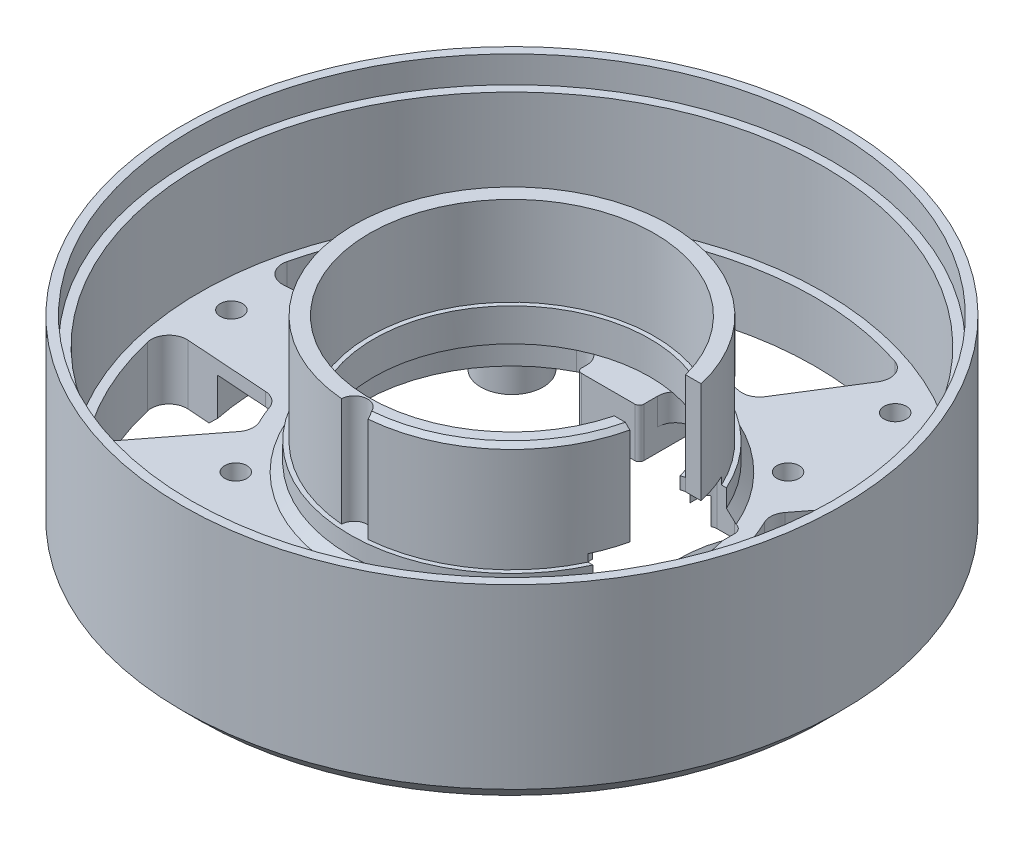
SolidWorks part; units mm, degrees
ref_plane "Front Plane" through (0, 0, 0) normal (0, 0, 1) x (1, 0, 0)
ref_plane "Top Plane" through (0, 0, 0) normal (0, 1, 0) x (1, 0, 0)
ref_plane "Right Plane" through (0, 0, 0) normal (1, 0, 0) x (0, 0, -1)
ref_axis "Axis1" through (0, 0, 0) along (0, 1, 0)
sketch "Sketch1" plane through (0, 0, 0) normal (0, 0, 1) x (1, 0, 0)
  line L0 (0, 0) -> (0, -50277.2651) construction
  line L1 (-17.7, 6) -> (-17.7, -6.2)
  line L2 (-17.7, -6.2) -> (-18.2, -6.2)
  line L3 (-18.2, -6.2) -> (-18.2, -8.2)
  line L4 (-19.2, -9.2) -> (-35, -9.2)
  line L7 (-35, -9.2) -> (-35, 3)
  line L8 (-35, 3) -> (-36, 3)
  line L9 (-36, 3) -> (-36, 6)
  line L10 (-36, 6) -> (-37, 6)
  line L11 (-37, 6) -> (-37, -13.9)
  line L12 (-35, -15.9) -> (-28, -15.9)
  line L13 (-28, -15.9) -> (-28, -10.7)
  line L14 (-28, -10.7) -> (-16.7, -10.7)
  line L23 (-16, -4) -> (-16, 6)
  line L24 (-16, 6) -> (-17.7, 6)
  line L25 (-14.9533, -4) -> (14.9533, -4) construction
  line L26 (19.25, 6) -> (-19.25, 6) construction
  line L27 (-34, 8) -> (-34, -6) construction
  line L28 (-19.25, -6) -> (19.25, -6) construction
  line L31 (-16, -4) -> (-15.5, -4)
  line L32 (11.5, -15.9) -> (-11.5, -15.9) construction
  line L37 (-16.7, -10.7) -> (-16.7, -7.7)
  line L38 (-16.7, -7.7) -> (-15.5, -7.7)
  line L42 (-37, -13.9) -> (-35, -15.9)
  line L44 (-18.2, -8.2) -> (-19.2, -9.2)
  line L50 (-15.5, -4) -> (-15.5, -7.7)
  point P6 (-18.2, -9.2)
  point P15 (-37, -15.9)
  point P31 (-31.5, -15.9)
  dimension "D1" = 35.4
  dimension "D2" = 32
  dimension "D3" = 0.5
  dimension "D4" = 3
  dimension "D5" = 1
  dimension "D6" = 1.5
  dimension "D7" = 0.2
  dimension "D8" = 2
  dimension "D9" = 3
  dimension "D10" = 72
  dimension "D11" = 1.5
  dimension "D12" = 0.5
  dimension "D13" = 63
  dimension "D14" = 1.5
revolve "Revolve1" add sketch "Sketch1" angle 360 about L0
sketch "Sketch2" plane through (0, 0, 0) normal (0, 1, 0) x (1, 0, 0)
  circle A0 centre (0, -17.7) radius 1.5
  circle A1 centre (0, 0) radius 17.7 construction
  circle A2 centre (0, 0) radius 17.7 construction
  dimension "D1" = 3
extrude "Cut-Extrude2" cut sketch "Sketch2" along normal up to next and the other way up to surface other way up to face at (0, -6.2, 18.2)
sketch "Sketch3" plane through (0, 0, 0) normal (0, 1, 0) x (1, 0, 0)
  circle A0 centre (-15.5, -15.5) radius 3.5
  circle A1 centre (15.5, -15.5) radius 3.5
  circle A2 centre (15.5, 15.5) radius 3.5
  circle A3 centre (-15.5, 15.5) radius 3.5
  dimension "D1" = 7
extrude "Boss-Extrude1" add sketch "Sketch3" against normal up to surface (4 mm away) from surface at -10.7 starting at face at (0, -10.7, 16.7)
hole_wizard "M3x0.5 Tapped Hole1" positions "Sketch4" profile "Sketch6" tap size "M3x0.5" standard "ANSI Metric" end condition through all
sketch "Sketch4" plane through (0, -14.7, 0) normal (0, -1, 0) x (-1, 0, 0)
  point P0 (-15.5, 15.5)
  point P3 (15.5, 15.5)
  point P6 (15.5, -15.5)
  point P9 (-15.5, -15.5)
sketch "Sketch6" plane through (15.5, -14.7, -15.5) normal (1, 0, 0) x (0, 0, -1)
  line L0 (0, 0) -> (0, 20.7)
  line L1 (0, 20.7) -> (1.25, 20.7)
  line L2 (1.25, 20.7) -> (1.25, 0.35)
  line L3 (1.25, 0.35) -> (1.6, 0)
  line L5 (1.6, 0) -> (0, 0)
  line L6 (-1.25, 0.35) -> (-1.6, 0) construction
  line L11 (0, -6.35) -> (0, 107.95) construction
  dimension "Thru Tap Drill Dia." = 2.5
  dimension "Thru Tap Drill Depth" = 20.7
  dimension "Near C'Sink Dia." = 3.2
  dimension "Near C'Sink Angle" = 90
cosmetic thread "Hole Thread5" parameters "D2"=3
cosmetic thread "Hole Thread6" parameters "D2"=3
cosmetic thread "Hole Thread7" parameters "D2"=3
cosmetic thread "Hole Thread8" parameters "D2"=3
sketch "Sketch7" plane through (0, 0, 0) normal (0, 1, 0) x (1, 0, 0)
  line L0 (-4.2, 18.5) -> (1.8, 12.5) construction
  line L1 (-4.2, 12) -> (1.8, 12)
  line L2 (-4.7, 12.5) -> (-4.7, 18.5)
  line L3 (-4.2, 19) -> (1.8, 19)
  line L4 (2.3, 12.5) -> (2.3, 18.5)
  arc A0 (1.8, 12) -> (2.3, 12.5) centre (1.8, 12.5) ccw
  arc A1 (-4.7, 18.5) -> (-4.2, 19) centre (-4.2, 18.5) cw
  arc A2 (1.8, 19) -> (2.3, 18.5) centre (1.8, 18.5) cw
  arc A3 (-4.2, 12) -> (-4.7, 12.5) centre (-4.2, 12.5) cw
  point P12 (-1.2, 15.5)
  dimension "D1" = 0.5
  dimension "D2" = 15.5
  dimension "D3" = 1.2
  dimension "D4" = 7
  dimension "D5" = 7
extrude "Boss-Extrude2" add sketch "Sketch7" against normal offset from surface (5.5 mm away) 1.5 from surface at -7.7 starting at face at (0, -7.7, 15.5)
sketch "Sketch10" plane through (0, 0, 0) normal (0, 1, 0) x (1, 0, 0)
  line L1 (15.5, 4) -> (17.5, 4)
  line L2 (14.5, 3) -> (14.5, -3)
  line L3 (15.5, -4) -> (17.5, -4)
  line L4 (18.5, 3) -> (18.5, -3)
  line L5 (14.5, 4) -> (18.5, -4) construction
  line L6 (14.5, -4) -> (18.5, 4) construction
  arc A0 (17.5, -4) -> (18.5, -3) centre (17.5, -3) ccw
  arc A1 (17.5, 4) -> (18.5, 3) centre (17.5, 3) cw
  arc A2 (14.5, -3) -> (15.5, -4) centre (15.5, -3) ccw
  arc A3 (15.5, 4) -> (14.5, 3) centre (15.5, 3) ccw
  circle A4 centre (0, 0) radius 16 construction
  circle A5 centre (0, 0) radius 16 construction
  point P0 (16.5, 0)
  point P5 (16, 0)
  dimension "D1" = 1
  dimension "D3" = 4
  dimension "D4" = 8
  dimension "D5" = 2.5
extrude "Cut-Extrude5" cut sketch "Sketch10" against normal through all both and the other way through all
chamfer "Chamfer1" distance 0.5 angle 45 1 edges at (11.5884, 6, 13.379)
hole_wizard "M3x0.5 Tapped Hole2" positions "Sketch11" profile "Sketch12" tap size "M3x0.5" standard "ANSI Metric" end condition through all
sketch "Sketch11" plane through (0, -15.9, 0) normal (0, -1, 0) x (-1, 0, 0)
  circle A0 centre (0, 0) radius 31.5 construction
  point P0 (-31.5, 0)
  dimension "D2" = 63
sketch "Sketch12" plane through (31.5, -15.9, 0) normal (1, 0, 0) x (0, 0, -1)
  line L0 (0, 0) -> (0, 21.9)
  line L1 (0, 21.9) -> (1.25, 21.9)
  line L2 (1.25, 21.9) -> (1.25, 0.35)
  line L3 (1.25, 0.35) -> (1.6, 0)
  line L5 (1.6, 0) -> (0, 0)
  line L6 (-1.25, 0.35) -> (-1.6, 0) construction
  line L11 (0, -6.35) -> (0, 107.95) construction
  dimension "Thru Tap Drill Dia." = 2.5
  dimension "Thru Tap Drill Depth" = 21.9
  dimension "Near C'Sink Dia." = 3.2
  dimension "Near C'Sink Angle" = 90
cosmetic thread "Hole Thread12" parameters "D2"=3
pattern_circular "CirPattern2" count 6 over 360 about axis through (0, 0, 0) along (0, 1, 0) of "M3x0.5 Tapped Hole2"
sketch "Sketch13" plane through (0, 0, 0) normal (0, 1, 0) x (1, 0, 0)
  line L0 (0, 0) -> (-50000, 0) construction
  line L1 (0, 0) -> (0, 50000) construction
  line L4 (-11.773, 29.3067) -> (-6.8945, 21.5451)
  line L6 (11.773, 29.3067) -> (6.8945, 21.5451)
  line L7 (11.773, -29.3067) -> (6.8945, -21.5451)
  line L8 (-11.773, -29.3067) -> (-6.8945, -21.5451)
  line L17 (19.2664, 11.3995) -> (25.0786, 18.9201)
  line L18 (31.0063, 5.364) -> (21.6421, 6.0019)
  line L19 (31.0063, -5.364) -> (21.6421, -6.0019)
  line L20 (19.2664, -11.3995) -> (25.0786, -18.9201)
  line L21 (-19.2664, -11.3995) -> (-25.0786, -18.9201)
  line L22 (-31.0063, -5.364) -> (-21.6421, -6.0019)
  line L23 (-31.0063, 5.364) -> (-21.6421, 6.0019)
  line L24 (-19.2664, 11.3995) -> (-25.0786, 18.9201)
  arc A0 (-10.7097, 32.2692) -> (10.7097, 32.2692) centre (0, 0) cw
  arc A5 (-4.7528, 20.6604) -> (4.7528, 20.6604) centre (0, 0) cw
  circle A16 centre (0, 0) radius 35 construction
  arc A17 (-4.7528, -20.6604) -> (4.7528, -20.6604) centre (0, 0) ccw
  arc A18 (-10.7097, -32.2692) -> (10.7097, -32.2692) centre (0, 0) ccw
  arc A27 (19.0516, 9.2992) -> (19.9006, 7.3079) centre (0, 0) cw
  arc A28 (28.3274, 18.8032) -> (33.0887, 7.8193) centre (0, 0) cw
  arc A29 (28.3274, -18.8032) -> (33.0887, -7.8193) centre (0, 0) ccw
  arc A30 (19.0516, -9.2992) -> (19.9006, -7.3079) centre (0, 0) ccw
  arc A31 (-19.0516, -9.2992) -> (-19.9006, -7.3079) centre (0, 0) cw
  arc A32 (-28.3274, -18.8032) -> (-33.0887, -7.8193) centre (0, 0) cw
  arc A33 (-28.3274, 18.8032) -> (-33.0887, 7.8193) centre (0, 0) ccw
  arc A34 (-19.0516, 9.2992) -> (-19.9006, 7.3079) centre (0, 0) ccw
  arc A35 (-19.9006, 7.3079) -> (-21.6421, 6.0019) centre (-21.778, 7.9973) cw
  arc A36 (-19.0516, 9.2992) -> (-19.2664, 11.3995) centre (-20.8489, 10.1765) ccw
  arc A37 (-33.0887, 7.8193) -> (-31.0063, 5.364) centre (-31.1423, 7.3593) ccw
  arc A38 (-28.3274, 18.8032) -> (-25.0786, 18.9201) centre (-26.6611, 17.6971) cw
  arc A39 (-33.0887, -7.8193) -> (-31.0063, -5.364) centre (-31.1423, -7.3593) cw
  arc A40 (-28.3274, -18.8032) -> (-25.0786, -18.9201) centre (-26.6611, -17.6971) ccw
  arc A41 (-19.9006, -7.3079) -> (-21.6421, -6.0019) centre (-21.778, -7.9973) ccw
  arc A42 (-19.0516, -9.2992) -> (-19.2664, -11.3995) centre (-20.8489, -10.1765) cw
  arc A43 (19.9006, -7.3079) -> (21.6421, -6.0019) centre (21.778, -7.9973) cw
  arc A44 (19.0516, -9.2992) -> (19.2664, -11.3995) centre (20.8489, -10.1765) ccw
  arc A45 (33.0887, -7.8193) -> (31.0063, -5.364) centre (31.1423, -7.3593) ccw
  arc A46 (28.3274, -18.8032) -> (25.0786, -18.9201) centre (26.6611, -17.6971) cw
  arc A47 (33.0887, 7.8193) -> (31.0063, 5.364) centre (31.1423, 7.3593) cw
  arc A48 (28.3274, 18.8032) -> (25.0786, 18.9201) centre (26.6611, 17.6971) ccw
  arc A49 (10.7097, -32.2692) -> (11.773, -29.3067) centre (10.0797, -30.371) ccw
  arc A50 (-10.7097, -32.2692) -> (-11.773, -29.3067) centre (-10.0797, -30.371) cw
  arc A51 (4.7528, -20.6604) -> (6.8945, -21.5451) centre (5.2012, -22.6095) cw
  arc A52 (-4.7528, -20.6604) -> (-6.8945, -21.5451) centre (-5.2012, -22.6095) ccw
  arc A53 (19.9006, 7.3079) -> (21.6421, 6.0019) centre (21.778, 7.9973) ccw
  arc A54 (4.7528, 20.6604) -> (6.8945, 21.5451) centre (5.2012, 22.6095) ccw
  arc A55 (-4.7528, 20.6604) -> (-6.8945, 21.5451) centre (-5.2012, 22.6095) cw
  arc A56 (10.7097, 32.2692) -> (11.773, 29.3067) centre (10.0797, 30.371) cw
  arc A57 (19.0516, 9.2992) -> (19.2664, 11.3995) centre (20.8489, 10.1765) cw
  arc A58 (-10.7097, 32.2692) -> (-11.773, 29.3067) centre (-10.0797, 30.371) ccw
  arc A59 (-4.6855, 18.6195) -> (-2.7641, 19) centre (0, 0) ccw construction
  point P9 (0, 21.2)
  point P10 (0, 34)
  point P50 (-20.3055, 6.093)
  point P53 (-18.4823, 10.3849)
  point P56 (-33.602, 5.1871)
  point P59 (-26.7125, 21.0343)
  point P62 (-33.602, -5.1871)
  point P65 (-26.7125, -21.0343)
  point P68 (-20.3055, -6.093)
  point P71 (-18.4823, -10.3849)
  point P74 (20.3055, -6.093)
  point P77 (18.4823, -10.3849)
  point P80 (33.602, -5.1871)
  point P83 (26.7125, -21.0343)
  point P86 (33.602, 5.1871)
  point P89 (26.7125, 21.0343)
  point P92 (13.0786, -31.3839)
  point P95 (-13.0786, -31.3839)
  point P98 (6.1118, -20.2999)
  point P101 (-6.1118, -20.2999)
  point P104 (20.3055, 6.093)
  point P107 (6.1118, 20.2999)
  point P110 (-6.1118, 20.2999)
  point P113 (13.0786, 31.3839)
  point P116 (18.4823, 10.3849)
  point P119 (-13.0786, 31.3839)
  dimension "D1" = 2
  dimension "D2" = 1
  dimension "D3" = 2
extrude "Cut-Extrude6" cut sketch "Sketch13" against normal through all
fillet "Fillet1" radius 2 2 edges at (2.3, -9.2, -16.5409) (-4.7, -9.2, -16.025)
sketch "Sketch14" plane through (0, 0, 0) normal (0, 1, 0) x (1, 0, 0)
  line L0 (0, 0) -> (16.5, 0) construction
  line L1 (18.5, 3) -> (18.5, -3) construction
  line L6 (15.5, -7.5) -> (17.5, -7.5)
  line L7 (14.5, -6.5) -> (14.5, 6.5)
  line L8 (15.5, 7.5) -> (17.5, 7.5)
  line L9 (18.5, -6.5) -> (18.5, 6.5)
  line L10 (14.5, -7.5) -> (18.5, 7.5) construction
  line L11 (14.5, 7.5) -> (18.5, -7.5) construction
  line L12 (14.5, 3) -> (14.5, -3) construction
  arc A7 (17.5, -7.5) -> (18.5, -6.5) centre (17.5, -6.5) ccw
  arc A8 (14.5, 6.5) -> (15.5, 7.5) centre (15.5, 6.5) cw
  arc A9 (15.5, -7.5) -> (14.5, -6.5) centre (15.5, -6.5) cw
  arc A10 (17.5, 7.5) -> (18.5, 6.5) centre (17.5, 6.5) cw
  dimension "D1" = 1
  dimension "D2" = 13
extrude "Cut-Extrude7" cut sketch "Sketch14" along normal offset from surface 11.38 and the other way through all from surface
sketch "Sketch15" plane through (0, -10.7, 0) normal (0, -1, 0) x (1, 0, 0)
  line L1 (14.5, 5.4772) -> (14.5, 6.5)
  line L11 (14.5, 5.4772) -> (14.5, 6.5)
  arc A1 (14.9905, 7.3604) -> (-7.6116, -14.8645) centre (0, 0) ccw
  arc A9 (-7.6116, -14.8645) -> (-5.3403, -14.551) centre (-6.7, -13.0843) ccw
  arc A10 (-7.6116, -14.8645) -> (-5.3403, -14.551) centre (-6.7, -13.0843) ccw
  arc A11 (14.5, 5.4772) -> (-5.3403, -14.551) centre (0, 0) ccw
  arc A12 (14.5, 5.4772) -> (-5.3403, -14.551) centre (0, 0) ccw
  arc A18 (14.9905, 7.3604) -> (14.5, 6.5) centre (15.5, 6.5) ccw
  arc A20 (14.9905, 7.3604) -> (14.5, 6.5) centre (15.5, 6.5) ccw
  arc A21 (14.9905, 7.3604) -> (-7.6116, -14.8645) centre (0, 0) ccw
  dimension "D1" = 0
extrude "Boss-Extrude3" [suppressed] add sketch "Sketch15" against normal up to surface (3 mm away)
chamfer "Chamfer2" distance 1 angle 45 6 edges at (28, -15.9, 0) (17.1305, -15.9, 22.1482) (-17.1305, -15.9, 22.1482) (-28, -15.9, 0) (-17.1305, -15.9, -22.1482) (17.1305, -15.9, -22.1482)
sketch "Sketch16" plane through (0, 0, 0) normal (0, 0, 1) x (1, 0, 0)
  line L0 (-17.7, -6.2) -> (-18.2, -6.2)
  line L1 (-18.2, -6.2) -> (-18.2, -8.2)
  line L2 (-18.2, -8.2) -> (-19.2, -9.2)
  line L3 (-19.2, -9.2) -> (-23.3334, -9.2)
  line L4 (-19.2, -9.2) -> (-35, -9.2) construction
  line L5 (-23.3334, -9.2) -> (-23.3334, -3.0666)
  line L6 (-23.3334, -3.0666) -> (-17.7, -3.0666)
  line L7 (-17.7, 6) -> (-17.7, -6.2) construction
  line L8 (-17.7, -3.0666) -> (-17.7, -6.2)
revolve "Cut-Revolve1" cut sketch "Sketch16" angle 360 about axis through (0, 0, 0) along (0, 1, 0)
fillet "Fillet2" [suppressed] radius 0.5
